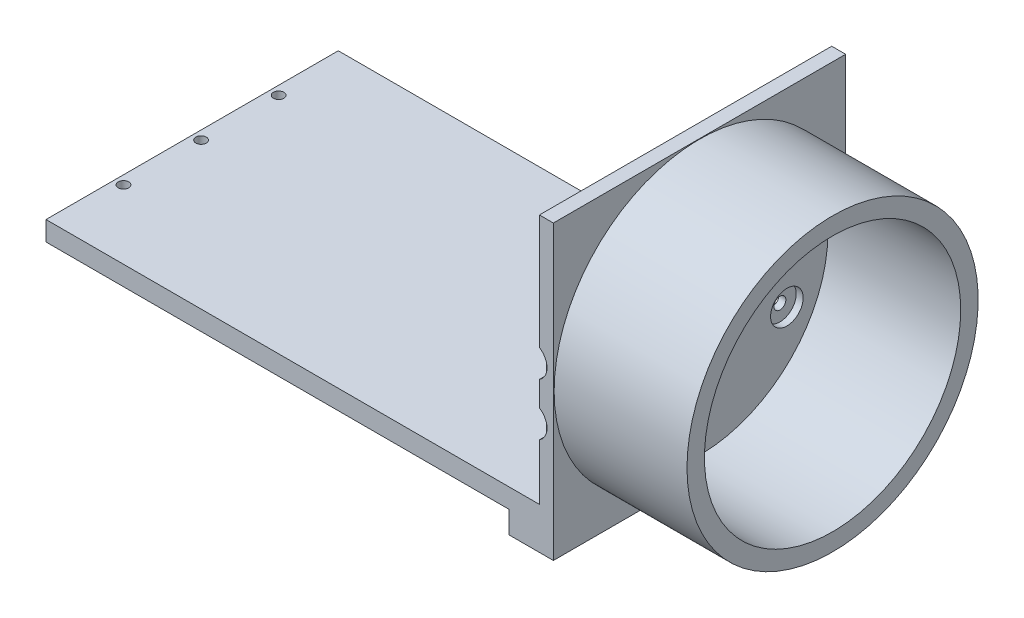
SolidWorks part; units mm, degrees
ref_plane "Front Plane" through (0, 0, 0) normal (0, 0, 1) x (1, 0, 0)
ref_plane "Top Plane" through (0, 0, 0) normal (0, 1, 0) x (1, 0, 0)
ref_plane "Right Plane" through (0, 0, 0) normal (1, 0, 0) x (0, 0, -1)
sketch "Sketch3" plane through (0, 0, 0) normal (0, 1, 0) x (1, 0, 0)
  line L0 (-38.8297, 34.4457) -> (-38.8297, -49.3743)
  line L1 (-38.8297, -49.3743) -> (106.6703, -49.3743)
  line L2 (106.6703, -49.3743) -> (106.6703, 34.4457)
  line L3 (106.6703, 34.4457) -> (-38.8297, 34.4457)
  dimension "D1" = 83.82
  dimension "D2" = 145.5
extrude "Boss-Extrude1" add sketch "Sketch3" along normal blind 83.82
sketch "Sketch4" plane through (0, 83.82, 0) normal (0, 1, 0) x (1, 0, 0)
  line L0 (-38.8297, 34.4457) -> (-38.8297, -44.8663)
  line L1 (-38.8297, 34.4457) -> (-38.8297, -49.3743) construction
  line L2 (-38.8297, -44.8663) -> (102.6703, -44.8663)
  line L3 (102.6703, -44.8663) -> (102.6703, 34.4457)
  line L4 (106.6703, 34.4457) -> (-38.8297, 34.4457) construction
  line L5 (102.6703, 34.4457) -> (-38.8297, 34.4457)
  dimension "D1" = 79.312
  dimension "D2" = 141.5
extrude "Cut-Extrude1" cut sketch "Sketch4" against normal blind 71.882
sketch "Sketch5" plane through (106.6703, 0, 0) normal (1, 0, 0) x (0, 0, -1)
  line L0 (-32.4113, 83.82) -> (-32.4113, 11.938) construction
  line L1 (-44.8663, 83.82) -> (34.4457, 83.82) construction
  line L2 (-44.8663, 11.938) -> (34.4457, 11.938) construction
  line L3 (-7.4113, 83.82) -> (-7.4113, 11.938) construction
  line L4 (17.5887, 83.82) -> (17.5887, 11.938) construction
  line L5 (34.4457, 54.438) -> (-44.8663, 54.438) construction
  line L6 (34.4457, 11.938) -> (34.4457, 83.82) construction
  line L7 (-44.8663, 11.938) -> (-44.8663, 83.82) construction
  line L8 (34.4457, 41.938) -> (-44.8663, 41.938) construction
  line L9 (34.4457, 29.438) -> (-44.8663, 29.438) construction
  line L10 (-44.8663, 11.938) -> (-44.8663, 83.82) construction
  line L11 (34.4457, 11.938) -> (-44.8663, 11.938) construction
  circle A0 centre (-7.4113, 41.938) radius 12.7
  dimension "D1" = 12.455
  dimension "D2" = 37.455
  dimension "D3" = 62.455
  dimension "D4" = 17.5
  dimension "D5" = 30
  dimension "D6" = 42.5
hole_wizard "CBORE for M3 Hex Head Cap Screw1" positions "Sketch6" profile "Sketch7" counterbore size "M3" standard "ISO" end condition up to next
sketch "Sketch6" plane through (106.6703, 0, 0) normal (1, 0, 0) x (0, 0, -1)
  line L0 (-32.4113, 83.82) -> (-32.4113, 11.938) construction
  line L1 (34.4457, 54.438) -> (-44.8663, 54.438) construction
  line L2 (17.5887, 83.82) -> (17.5887, 11.938) construction
  line L3 (34.4457, 29.438) -> (-44.8663, 29.438) construction
  point P0 (-32.4113, 54.438)
  point P6 (17.5887, 54.438)
  point P10 (17.5887, 29.438)
  point P14 (-32.4113, 29.438)
sketch "Sketch7" plane through (106.6703, 54.438, 32.4113) normal (0, 1, 0) x (0, 0, -1)
  line L0 (0, 0) -> (0, 4)
  line L1 (0, 4) -> (1.7, 4)
  line L3 (1.7, 4) -> (1.7, 2)
  line L4 (1.7, 2) -> (4.6755, 2)
  line L5 (4.6755, 2) -> (4.6755, 0)
  line L7 (4.6755, 0) -> (0, 0)
  line L11 (0, -6.35) -> (0, 107.95) construction
  dimension "Thru Hole Dia." = 3.4
  dimension "Thru Hole Depth" = 4
  dimension "C'Bore Dia." = 9.351
  dimension "C'Bore Depth" = 2
extrude "Cut-Extrude3" cut sketch "Sketch5" against normal up to next contours A0
sketch "Sketch8" plane through (0, 0, 49.3743) normal (0, 0, 1) x (1, 0, 0)
  line L0 (100.1703, 83.82) -> (100.1703, 11.938) construction
  line L1 (-38.8297, 83.82) -> (102.6703, 83.82) construction
  line L2 (102.6703, 11.938) -> (-38.8297, 11.938) construction
  line L3 (-36.3297, 83.82) -> (-36.3297, 11.938) construction
  line L4 (-38.8297, 11.938) -> (102.6703, 11.938) construction
  line L5 (102.6703, 46.938) -> (-38.8297, 46.938) construction
  line L6 (102.6703, 11.938) -> (102.6703, 83.82) construction
  line L7 (-38.8297, 11.938) -> (-38.8297, 83.82) construction
  line L8 (102.6703, 31.938) -> (-38.8297, 31.938) construction
  line L9 (102.6703, 11.938) -> (102.6703, 83.82) construction
  dimension "D1" = 2.5
  dimension "D2" = 139
  dimension "D3" = 20
  dimension "D4" = 35
hole_wizard "CBORE for M3 Hex Head Cap Screw2" positions "Sketch11" profile "Sketch12" counterbore size "M3" standard "ISO" end condition up to next
sketch "Sketch11" plane through (0, 0, 49.3743) normal (0, 0, 1) x (1, 0, 0)
  line L0 (100.1703, 83.82) -> (100.1703, 11.938) construction
  line L1 (102.6703, 46.938) -> (-38.8297, 46.938) construction
  line L2 (102.6703, 31.938) -> (-38.8297, 31.938) construction
  point P0 (100.1703, 46.938)
  point P6 (100.1703, 31.938)
sketch "Sketch12" plane through (100.1703, 46.938, 49.3743) normal (1, 0, 0) x (0, -1, 0)
  line L0 (0, 0) -> (0, 4.508)
  line L1 (0, 4.508) -> (1.7, 4.508)
  line L3 (1.7, 4.508) -> (1.7, 2)
  line L4 (1.7, 2) -> (4.6755, 2)
  line L5 (4.6755, 2) -> (4.6755, 0)
  line L7 (4.6755, 0) -> (0, 0)
  line L11 (0, -6.35) -> (0, 107.95) construction
  dimension "Thru Hole Dia." = 3.4
  dimension "Thru Hole Depth" = 4.508
  dimension "C'Bore Dia." = 9.351
  dimension "C'Bore Depth" = 2
hole_wizard "Ø3.0mm Dowel Hole1" positions "Sketch13" profile "Sketch14" hole size "Ø3.0" standard "ISO" end condition up to next
sketch "Sketch13" plane through (0, 0, 49.3743) normal (0, 0, 1) x (1, 0, 0)
  line L0 (-36.3297, 83.82) -> (-36.3297, 11.938) construction
  line L1 (102.6703, 46.938) -> (-38.8297, 46.938) construction
  line L2 (102.6703, 31.938) -> (-38.8297, 31.938) construction
  point P0 (-36.3297, 46.938)
  point P6 (-36.3297, 31.938)
sketch "Sketch14" plane through (-36.3297, 46.938, 49.3743) normal (1, 0, 0) x (0, -1, 0)
  line L0 (0, 0) -> (0, 4.508)
  line L1 (0, 4.508) -> (1.5, 4.508)
  line L2 (1.5, 4.508) -> (1.5, 0)
  line L5 (1.5, 0) -> (0, 0)
  line L11 (0, -6.35) -> (0, 107.95) construction
  dimension "Thru Hole Dia." = 3
  dimension "Thru Hole Depth" = 4.508
sketch "Sketch15" plane through (0, 0, 0) normal (0, -1, 0) x (-1, 0, 0)
  line L0 (-100.1703, -44.8663) -> (-100.1703, 34.4457) construction
  line L1 (38.8297, -44.8663) -> (-102.6703, -44.8663) construction
  line L2 (-102.6703, 34.4457) -> (38.8297, 34.4457) construction
  line L3 (36.3297, -44.8663) -> (36.3297, 34.4457) construction
  line L4 (38.8297, -44.8663) -> (-102.6703, -44.8663) construction
  line L5 (-102.6703, -29.6613) -> (38.8297, -29.6613) construction
  line L6 (-102.6703, -44.8663) -> (-102.6703, 34.4457) construction
  line L7 (38.8297, 34.4457) -> (38.8297, -44.8663) construction
  line L8 (-102.6703, -7.4113) -> (38.8297, -7.4113) construction
  line L9 (-102.6703, -44.8663) -> (-102.6703, 34.4457) construction
  line L10 (-102.6703, 14.8387) -> (38.8297, 14.8387) construction
  dimension "D1" = 2.5
  dimension "D2" = 139
  dimension "D3" = 15.205
  dimension "D4" = 37.455
  dimension "D5" = 59.705
hole_wizard "Ø3.0mm Dowel Hole2" positions "Sketch18" profile "Sketch19" hole size "Ø3.0" standard "ISO" end condition up to next
sketch "Sketch18" plane through (0, 0, 0) normal (0, -1, 0) x (-1, 0, 0)
  line L0 (36.3297, -44.8663) -> (36.3297, 34.4457) construction
  line L1 (-102.6703, -29.6613) -> (38.8297, -29.6613) construction
  line L2 (-102.6703, -7.4113) -> (38.8297, -7.4113) construction
  line L3 (-102.6703, 14.8387) -> (38.8297, 14.8387) construction
  point P0 (36.3297, -29.6613)
  point P6 (36.3297, -7.4113)
  point P10 (36.3297, 14.8387)
sketch "Sketch19" plane through (-36.3297, 0, 29.6613) normal (1, 0, 0) x (0, 0, -1)
  line L0 (0, 0) -> (0, 11.938)
  line L1 (0, 11.938) -> (1.5, 11.938)
  line L2 (1.5, 11.938) -> (1.5, 0)
  line L5 (1.5, 0) -> (0, 0)
  line L11 (0, -6.35) -> (0, 107.95) construction
  dimension "Thru Hole Dia." = 3
  dimension "Thru Hole Depth" = 11.938
hole_wizard "CBORE for M3 Hex Head Cap Screw3" positions "Sketch20" profile "Sketch21" counterbore size "M3" standard "ISO" end condition up to next
sketch "Sketch20" plane through (0, 0, 0) normal (0, -1, 0) x (-1, 0, 0)
  line L0 (-100.1703, -44.8663) -> (-100.1703, 34.4457) construction
  line L1 (-102.6703, -29.6613) -> (38.8297, -29.6613) construction
  line L2 (-102.6703, -7.4113) -> (38.8297, -7.4113) construction
  line L3 (-102.6703, 14.8387) -> (38.8297, 14.8387) construction
  point P0 (-100.1703, -29.6613)
  point P6 (-100.1703, -7.4113)
  point P10 (-100.1703, 14.8387)
sketch "Sketch21" plane through (100.1703, 0, 29.6613) normal (1, 0, 0) x (0, 0, -1)
  line L0 (0, 0) -> (0, 11.938)
  line L1 (0, 11.938) -> (1.7, 11.938)
  line L3 (1.7, 11.938) -> (1.7, 2)
  line L4 (1.7, 2) -> (4.6755, 2)
  line L5 (4.6755, 2) -> (4.6755, 0)
  line L7 (4.6755, 0) -> (0, 0)
  line L11 (0, -6.35) -> (0, 107.95) construction
  dimension "Thru Hole Dia." = 3.4
  dimension "Thru Hole Depth" = 11.938
  dimension "C'Bore Dia." = 9.351
  dimension "C'Bore Depth" = 2
sketch "Sketch22" plane through (106.6703, 0, 0) normal (1, 0, 0) x (0, 0, -1)
  circle A0 centre (-7.4113, 41.938) radius 41.75
extrude "Boss-Extrude3" add sketch "Sketch22" along normal blind 38.1
sketch "Sketch26" plane through (144.7703, 0, 0) normal (1, 0, 0) x (0, 0, -1)
  circle A0 centre (-7.4113, 41.938) radius 36.75
extrude "Cut-Extrude5" cut sketch "Sketch26" against normal blind 38.1
sketch "Sketch27" plane through (0, 83.82, 0) normal (0, 1, 0) x (1, 0, 0)
  line L0 (102.6703, -44.8663) -> (102.6703, -49.3743)
  line L1 (-38.8297, -49.3743) -> (106.6703, -49.3743) construction
  line L2 (102.6703, -49.3743) -> (-38.8297, -49.3743)
  line L3 (-38.8297, -49.3743) -> (-38.8297, -44.8663)
  line L4 (-38.8297, -44.8663) -> (102.6703, -44.8663)
extrude "Cut-Extrude7" cut sketch "Sketch27" against normal up to surface (71.882 mm away) up to face at (100.1703, 11.938, 31.3613)
sketch "Sketch28" plane through (0, 0, 0) normal (0, -1, 0) x (-1, 0, 0)
  line L0 (38.8297, -49.3743) -> (38.8297, 34.4457)
  line L1 (38.8297, 34.4457) -> (-93.898, 34.4457)
  line L2 (-106.6703, 34.4457) -> (38.8297, 34.4457) construction
  line L3 (-93.898, 34.4457) -> (-93.898, -49.3743)
  line L4 (38.8297, -49.3743) -> (-106.6703, -49.3743) construction
  line L5 (-93.898, -49.3743) -> (38.8297, -49.3743)
extrude "Cut-Extrude8" cut sketch "Sketch28" against normal blind 6.35
